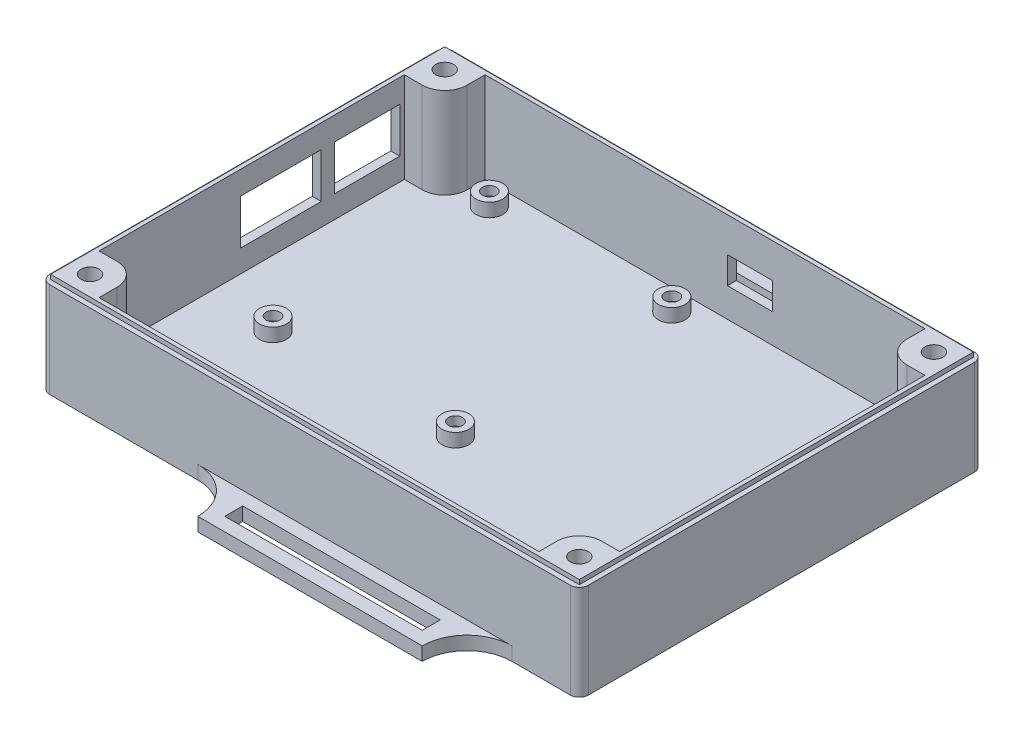
SolidWorks part; units mm, degrees
ref_plane "Front Plane" through (0, 0, 0) normal (0, 0, 1) x (1, 0, 0)
ref_plane "Top Plane" through (0, 0, 0) normal (0, 1, 0) x (1, 0, 0)
ref_plane "Right Plane" through (0, 0, 0) normal (1, 0, 0) x (0, 0, -1)
sketch "Sketch1" plane through (0, 0, 0) normal (0, 1, 0) x (1, 0, 0)
  line L1 (0, 0) -> (120, 0)
  line L2 (0, 0) -> (0, 90)
  line L3 (0, 90) -> (120, 90)
  line L4 (120, 0) -> (120, 90)
  dimension "D1" = 90
  dimension "D2" = 120
extrude "Boss-Extrude1" add sketch "Sketch1" along normal blind 22.2
shell "Shell1" thickness 2 removed face at (60, 22.2, -45)
sketch "Sketch2" plane through (0, 2, 0) normal (0, 1, 0) x (1, 0, 0)
  line L0 (2, 2) -> (118, 2) construction
  line L1 (118, 88) -> (2, 88) construction
  line L2 (2, 11) -> (11, 11)
  line L3 (2, 11) -> (2, 2)
  line L4 (2, 2) -> (118, 2) construction
  line L5 (2, 2) -> (11, 2)
  line L6 (11, 11) -> (11, 2)
  line L7 (2, 88) -> (2, 2) construction
  line L8 (109, 79) -> (118, 79)
  line L9 (118, 88) -> (118, 79)
  line L10 (109, 2) -> (118, 2)
  line L11 (109, 79) -> (109, 88)
  line L12 (118, 88) -> (109, 88)
  line L13 (109, 11) -> (109, 2)
  line L14 (118, 2) -> (118, 88) construction
  line L15 (109, 11) -> (118, 11)
  line L16 (118, 11) -> (118, 2)
  line L23 (2, 88) -> (11, 88)
  line L24 (2, 88) -> (2, 79)
  line L25 (2, 79) -> (11, 79)
  line L26 (11, 88) -> (11, 79)
  dimension "D1" = 9
  dimension "D2" = 9
  dimension "D3" = 9
  dimension "D4" = 9
  dimension "D5" = 9
  dimension "D6" = 9
  dimension "D7" = 9
  dimension "D8" = 9
extrude "Boss-Extrude2" add sketch "Sketch2" along normal up to surface (20.2 mm away) up to face at (60, 22.2, -45)
sketch "Sketch5" plane through (0, 22.2, 0) normal (0, 1, 0) x (1, 0, 0)
  line L1 (120, 90) -> (0, 90)
  line L2 (120, 90) -> (120, 0)
  line L3 (120, 0) -> (0, 0)
  line L4 (0, 90) -> (0, 0)
  line L5 (1.1, 1.1) -> (118.9, 1.1)
  line L6 (1.1, 1.1) -> (1.1, 88.9)
  line L7 (1.1, 88.9) -> (118.9, 88.9)
  line L8 (118.9, 1.1) -> (118.9, 88.9)
  dimension "D1" = 1.1
  dimension "D2" = 1.1
  dimension "D3" = 1.1
  dimension "D4" = 1.1
extrude "Cut-Extrude2" cut sketch "Sketch5" against normal blind 1
sketch "Sketch6" plane through (0, 22.2, 0) normal (0, 1, 0) x (1, 0, 0)
  line L0 (120, 0) -> (120, 90) construction
  line L1 (0, 0) -> (120, 0) construction
  line L3 (120, 90) -> (0, 90) construction
  line L5 (0, 90) -> (0, 0) construction
  line L7 (0, 0) -> (120, 0) construction
  circle A0 centre (114.5, 84.5) radius 2
  circle A1 centre (114.5, 5.5) radius 2
  circle A2 centre (5.5, 84.5) radius 2
  circle A3 centre (5.5, 5.5) radius 2
  dimension "D8" = 4
  dimension "D9" = 5.5
  dimension "D1" = 5.5
  dimension "D2" = 5.5
  dimension "D3" = 5.5
  dimension "D4" = 5.5
  dimension "D5" = 5.5
  dimension "D6" = 5.5
  dimension "D7" = 5.5
extrude "Cut-Extrude3" cut sketch "Sketch6" against normal blind 25
sketch "Sketch13" plane through (0, 0, 0) normal (0, -1, 0) x (1, 0, 0)
  circle A0 centre (114.5, -5.5) radius 3
  circle A1 centre (114.5, -84.5) radius 3
  circle A2 centre (5.5, -5.5) radius 3
  circle A3 centre (5.5, -84.5) radius 3
  dimension "D1" = 6
extrude "Cut-Extrude8" cut sketch "Sketch13" against normal blind 15
sketch "Sketch14" plane through (0, 0, 0) normal (0, 0, 1) x (1, 0, 0)
  line L1 (95, 0) -> (45, 0)
  line L2 (95, 0) -> (95, 3)
  line L3 (95, 3) -> (45, 3)
  line L4 (45, 0) -> (45, 3)
  line L5 (120, 21.2) -> (120, 0) construction
  line L6 (0, 0) -> (120, 0) construction
  dimension "D1" = 0
  dimension "D2" = 3
  dimension "D3" = 50
  dimension "D4" = 25
extrude "Boss-Extrude4" add sketch "Sketch14" along normal blind 10
sketch "Sketch15" plane through (0, 0, 0) normal (0, -1, 0) x (-1, 0, 0)
  line L1 (-92, -3) -> (-48, -3)
  line L2 (-92, -3) -> (-92, -7)
  line L3 (-92, -7) -> (-48, -7)
  line L4 (-48, -3) -> (-48, -7)
  line L6 (-95, -10) -> (-45, -10) construction
  line L7 (-95, 0) -> (-45, 0) construction
  line L8 (-45, -10) -> (-45, 0) construction
  line L9 (-95, -10) -> (-95, 0) construction
  dimension "D1" = 3
  dimension "D2" = 3
  dimension "D3" = 3
  dimension "D4" = 3
extrude "Cut-Extrude9" cut sketch "Sketch15" against normal blind 10
sketch "Sketch16" plane through (0, 0, -90) normal (0, 0, -1) x (-1, 0, 0)
  line L1 (-95, 3) -> (-45, 3)
  line L2 (-95, 3) -> (-95, 0)
  line L3 (-95, 0) -> (-45, 0)
  line L4 (-45, 3) -> (-45, 0)
  line L5 (-120, 21.2) -> (-120, 0) construction
  line L6 (-120, 0) -> (0, 0) construction
  dimension "D1" = 3
  dimension "D2" = 0
  dimension "D3" = 25
  dimension "D4" = 50
extrude "Boss-Extrude5" add sketch "Sketch16" along normal blind 10
sketch "Sketch17" plane through (0, 0, 0) normal (0, -1, 0) x (-1, 0, 0)
  line L0 (-45, 90) -> (-95, 90) construction
  line L1 (-92, 97) -> (-48, 97)
  line L2 (-92, 97) -> (-92, 93)
  line L3 (-92, 93) -> (-48, 93)
  line L4 (-48, 97) -> (-48, 93)
  line L5 (-45, 100) -> (-95, 100) construction
  line L8 (-95, 100) -> (-95, 90) construction
  line L9 (-45, 100) -> (-45, 90) construction
  dimension "D1" = 3
  dimension "D2" = 3
  dimension "D3" = 3
  dimension "D4" = 3
extrude "Cut-Extrude10" cut sketch "Sketch17" against normal blind 10
sketch "Sketch22" plane through (0, 0, 0) normal (-1, 0, 0) x (0, 0, 1)
  line L0 (-90, 0) -> (0, 0) construction
  line L1 (-78, 17) -> (-63.5, 17)
  line L2 (-78, 17) -> (-78, 7)
  line L3 (-78, 7) -> (-63.5, 7)
  line L4 (-63.5, 17) -> (-63.5, 7)
  line L5 (-60.5, 7) -> (-42.5, 7)
  line L6 (-60.5, 7) -> (-60.5, 17)
  line L7 (-60.5, 17) -> (-42.5, 17)
  line L8 (-42.5, 7) -> (-42.5, 17)
  line L9 (-90, 21.2) -> (-90, 0) construction
  dimension "D1" = 18
  dimension "D2" = 3
  dimension "D3" = 10
  dimension "D4" = 7
  dimension "D5" = 10
  dimension "D6" = 14.5
  dimension "D7" = 7
  dimension "D8" = 12
extrude "Cut-Extrude15" cut sketch "Sketch22" against normal blind 10
sketch "Sketch23" plane through (0, 0, -90) normal (0, 0, -1) x (-1, 0, 0)
  line L1 (-75, 8.5) -> (-65, 8.5)
  line L2 (-75, 8.5) -> (-75, 14.5)
  line L3 (-75, 14.5) -> (-65, 14.5)
  line L4 (-65, 8.5) -> (-65, 14.5)
  line L5 (-120, 21.2) -> (-120, 0) construction
  line L6 (-120, 0) -> (-95, 0) construction
  dimension "D1" = 8.5
  dimension "D2" = 6
  dimension "D3" = 45
  dimension "D4" = 10
extrude "Cut-Extrude16" cut sketch "Sketch23" against normal blind 10
fillet "Fillet1" radius 10 4 edges at (95, 1.5, -90) (95, 1.5, 0) (45, 1.5, 0) (45, 1.5, -90)
fillet "Fillet4" radius 5 4 edges at (109, 12.1, -79) (109, 12.1, -11) (11, 12.1, -11) (11, 12.1, -79)
fillet "Fillet9" radius 2 4 edges at (0, 10.6, -90) (120, 10.6, -90) (120, 10.6, 0) (0, 10.6, 0)
sketch "Sketch26" plane through (0, 2, 0) normal (0, 1, 0) x (1, 0, 0)
  line L0 (109, 88) -> (11, 88) construction
  line L1 (2, 79) -> (2, 11) construction
  circle A0 centre (16.75, 83.2) radius 3
  circle A1 centre (16.75, 35) radius 3
  circle A2 centre (57.4, 35) radius 3
  circle A3 centre (57.4, 83.2) radius 3
  dimension "D1" = 6
  dimension "D2" = 4.8
  dimension "D3" = 53
  dimension "D4" = 55.4
  dimension "D5" = 55.4
  dimension "D6" = 14.75
  dimension "D7" = 14.75
  dimension "D8" = 53
  dimension "D9" = 4.8
extrude "Boss-Extrude7" add sketch "Sketch26" along normal blind 3
sketch "Sketch27" plane through (0, 5, 0) normal (0, 1, 0) x (1, 0, 0)
  circle A0 centre (57.4, 83.2) radius 1.55
  circle A1 centre (57.4, 35) radius 1.55
  circle A2 centre (16.75, 35) radius 1.55
  circle A3 centre (16.75, 83.2) radius 1.55
  dimension "D1" = 3.1
extrude "Cut-Extrude17" cut sketch "Sketch27" against normal blind 2
